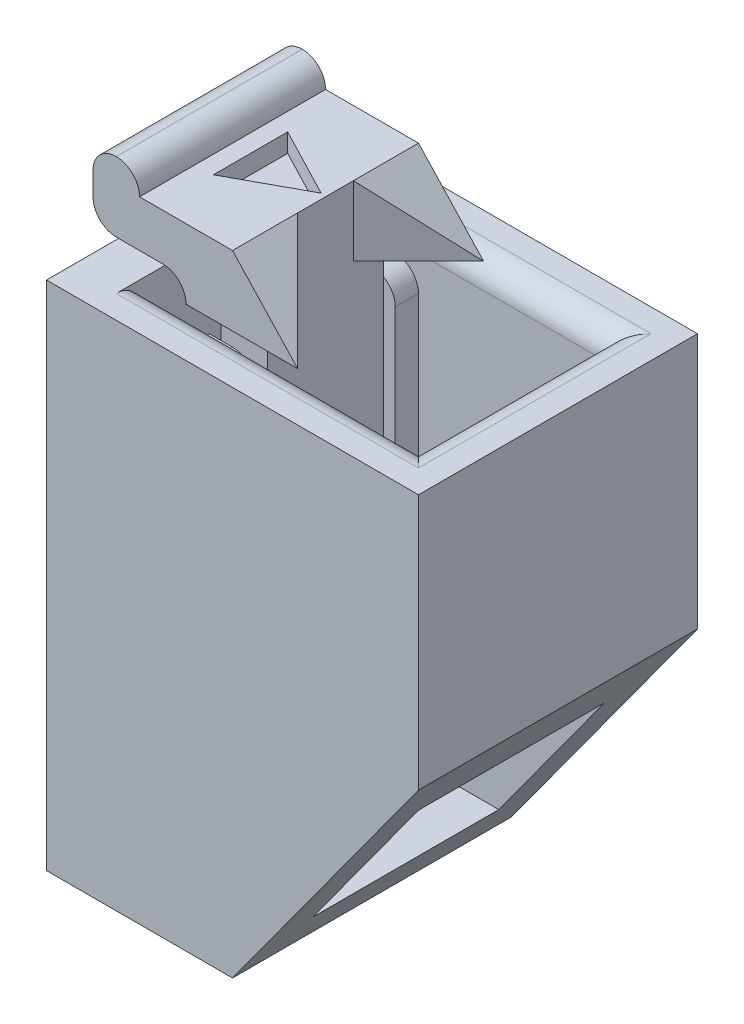
SolidWorks part; units mm, degrees
ref_plane "Front Plane" through (0, 0, 0) normal (0, 0, 1) x (1, 0, 0)
ref_plane "Top Plane" through (0, 0, 0) normal (0, 1, 0) x (1, 0, 0)
ref_plane "Right Plane" through (0, 0, 0) normal (1, 0, 0) x (0, 0, -1)
sketch "BaseSketch" plane through (0, 0, 0) normal (0, 1, 0) x (1, 0, 0)
  line L1 (-6.2677, 3.9685) -> (9.7323, 3.9685)
  line L2 (-6.2677, 3.9685) -> (-6.2677, -8.0315)
  line L3 (-6.2677, -8.0315) -> (9.7323, -8.0315)
  line L4 (9.7323, 3.9685) -> (9.7323, -8.0315)
  dimension "D1" = 16
  dimension "D2" = 12
extrude "BaseExtrude" add sketch "BaseSketch" along normal blind 2
sketch "SlotSketch" plane through (0, 2, 0) normal (0, 1, 0) x (1, 0, 0)
  line L10 (-2.2677, 0.9685) -> (-0.2677, 0.9685)
  line L11 (-2.2677, 1.9685) -> (-4.2677, 1.9685)
  line L12 (-2.2677, 1.9685) -> (-2.2677, 0.9685)
  line L13 (-0.2677, -6.0315) -> (7.7323, -6.0315)
  line L14 (7.7323, -6.0315) -> (7.7323, 1.9685)
  line L15 (-4.2677, -6.0315) -> (7.7323, -6.0315)
  line L16 (-4.2677, 1.9685) -> (-4.2677, -6.0315)
  line L17 (7.7323, 1.9685) -> (-4.2677, 1.9685)
  line L18 (7.7323, -6.0315) -> (7.7323, 1.9685)
  line L19 (-4.2677, -6.0315) -> (-2.2677, -6.0315)
  line L20 (-4.2677, 1.9685) -> (-4.2677, -6.0315)
  line L21 (7.7323, 1.9685) -> (-0.2677, 1.9685)
  line L22 (-0.2677, 1.9685) -> (-0.2677, 0.9685)
  line L23 (-2.2677, -5.0315) -> (-0.2677, -5.0315)
  line L24 (-2.2677, 0.4685) -> (-2.2677, -4.5315)
  line L25 (-2.2677, 0.4685) -> (-0.2677, 0.4685)
  line L26 (-2.2677, 0.4685) -> (-2.2677, -4.5315)
  line L27 (-2.2677, -4.5315) -> (-0.2677, -4.5315)
  line L28 (-0.2677, 0.4685) -> (-0.2677, -4.5315)
  line L29 (-0.2677, 0.4685) -> (-0.2677, -4.5315)
  line L30 (-2.2677, -5.0315) -> (-2.2677, -6.0315)
  line L31 (-0.2677, -5.0315) -> (-0.2677, -6.0315)
  line L33 (-6.2677, 3.9685) -> (9.7323, 3.9685)
  line L34 (-6.2677, 3.9685) -> (-6.2677, -8.0315)
  line L35 (-6.2677, -8.0315) -> (9.7323, -8.0315)
  line L36 (9.7323, 3.9685) -> (9.7323, -8.0315)
  line M5 (-6.2677, 3.9685) -> (-6.2677, -8.0315)
  line M6 (-6.2677, -8.0315) -> (9.7323, -8.0315)
  line M7 (9.7323, -8.0315) -> (9.7323, 3.9685)
  line M8 (9.7323, 3.9685) -> (-6.2677, 3.9685)
  dimension "D2" = 8
  dimension "D3" = 2
  dimension "D4" = 2
  dimension "D5" = 8
  dimension "D6" = 1
  dimension "D7" = 1
  dimension "D8" = 5
  dimension "D9" = 0.5
  dimension "D1" = 2
extrude "FlapExtrude" add sketch "SlotSketch" along normal blind 20.1 contours L25 L28 L27 L24
sketch "HandleBaseSketch" plane through (0, 22.1, 0) normal (0, 1, 0) x (1, 0, 0)
  line L0 (9.7323, 3.9685) -> (-6.2677, 3.9685) construction
  line L1 (-2.2677, 1.9685) -> (-0.2677, 1.9685)
  line L2 (-2.2677, 1.9685) -> (-2.2677, -6.0315)
  line L3 (-2.2677, -6.0315) -> (-0.2677, -6.0315)
  line L4 (-0.2677, 1.9685) -> (-0.2677, -6.0315)
  line L5 (-6.2677, -8.0315) -> (9.7323, -8.0315) construction
  dimension "D1" = 2
  dimension "D2" = 2
extrude "HandleBase" add sketch "HandleBaseSketch" along normal blind 3
sketch "TriangleBaseSketch" plane through (-0.2677, 0, 0) normal (1, 0, 0) x (0, 0, -1)
  line L0 (-6.0315, 22.1) -> (-3.2315, 22.1)
  line L1 (-3.2315, 22.1) -> (-3.2315, 25.1)
  line L2 (-6.0315, 25.1) -> (1.9685, 25.1) construction
  line L3 (-3.2315, 25.1) -> (-6.0315, 25.1)
  line L4 (-6.0315, 25.1) -> (-6.0315, 22.1)
  line L5 (1.9685, 22.1) -> (-0.8315, 22.1)
  line L6 (-0.8315, 22.1) -> (-0.8315, 25.1)
  line L7 (-0.8315, 25.1) -> (1.9685, 25.1)
  line L8 (1.9685, 25.1) -> (1.9685, 22.1)
extrude "PyramidExtrude" add sketch "TriangleBaseSketch" along normal blind 2.8
sketch "PyramidSideCutSketch" plane through (0, 0, -1.9685) normal (0, 0, -1) x (-1, 0, 0)
  line L0 (-2.5323, 22.1) -> (0.2677, 25.1)
  line L1 (0.2677, 25.1) -> (-2.5323, 25.1)
  line L2 (-2.5323, 25.1) -> (-2.5323, 22.1)
sketch "PyramidTopCutSketch" plane through (0, 25.1, 0) normal (0, 1, 0) x (1, 0, 0)
  line L0 (-0.2677, -3.2315) -> (2.5323, -6.0315)
  line L1 (2.5323, -6.0315) -> (2.5323, -3.2315)
  line L2 (2.5323, -3.2315) -> (-0.2677, -3.2315)
  line L3 (-0.2677, -0.8315) -> (2.5323, 1.9685)
  line L4 (2.5323, 1.9685) -> (2.5323, -0.8315)
  line L5 (2.5323, -0.8315) -> (-0.2677, -0.8315)
extrude "PyramidTopCut" cut sketch "PyramidTopCutSketch" against normal blind 3
extrude "PyramidSideCut" cut sketch "PyramidSideCutSketch" against normal through all contours L0 L1 L2
extrude "Boss-Extrude5" add sketch "SlotSketch<6>" along normal blind 3 contours L31 L23 L30 L19 L20 L11 L12 L10 L22 L21 L18 L13 M8 M5 M6 M7 | L12 L10 L22 L21 L18 L13 L31 L23 L30 L19 L20 L11 | L33 L36 L35 L34 region at (-1.2677, 2, -1.4685) region at (-1.2677, 2, 5.5315) region at (1.7323, 2, -3.7685)
sketch "SlotSketch<6>" plane through (0, 2, 0) normal (0, 1, 0) x (1, 0, 0) same geometry as "SlotSketch"
extrude "Sides" add sketch "SlotSketch<7>" along normal blind 20 contours L11 L20 L19 L30 L23 L31 L13 L18 L21 L22 L10 L12 | L33 L36 L35 L34
sketch "SlotSketch<7>" plane through (0, 2, 0) normal (0, 1, 0) x (1, 0, 0) same geometry as "SlotSketch"
sketch "Sketch7" plane through (-0.2677, 0, 0) normal (1, 0, 0) x (0, 0, -1)
  line L0 (-5.0315, 22) -> (-5.0315, 2) construction
  line L1 (-6.0315, 22) -> (-5.0315, 22)
  line L2 (-6.0315, 22) -> (-6.0315, 20.4974)
  line L3 (-6.0315, 20.4974) -> (-5.0315, 20.4974)
  line L4 (-5.0315, 22) -> (-5.0315, 20.4974)
  line L5 (1.9685, 22) -> (1.9685, 2) construction
  line L6 (0.9685, 22) -> (1.9685, 22)
  line L7 (0.9685, 22) -> (0.9685, 20.4974)
  line L8 (0.9685, 20.4974) -> (1.9685, 20.4974)
  line L9 (1.9685, 22) -> (1.9685, 20.4974)
extrude "WallClearanceCut" cut sketch "Sketch7" against normal blind 2
sketch "BaseTriangleCutSketch" plane through (0, 0, 8.0315) normal (0, 0, 1) x (1, 0, 0)
  line L0 (9.7323, 0) -> (1.7323, 0)
  line L1 (-6.2677, 0) -> (9.7323, 0) construction
  line L2 (1.7323, 0) -> (9.7323, 11)
  line L3 (9.7323, 22) -> (9.7323, 0) construction
  line L4 (9.7323, 11) -> (9.7323, 0)
extrude "BaseTriangleCut" cut sketch "BaseTriangleCutSketch" against normal through all
sketch "Sketch9" plane through (-2.2677, 0, 0) normal (-1, 0, 0) x (0, 0, 1)
  line L0 (6.0315, 25.1) -> (6.0315, 22.1) construction
  line L1 (-1.9685, 25.1) -> (6.0315, 25.1)
  line L2 (-1.9685, 25.1) -> (-1.9685, 23.1)
  line L3 (-1.9685, 23.1) -> (6.0315, 23.1)
  line L4 (6.0315, 25.1) -> (6.0315, 23.1)
extrude "Handle" add sketch "Sketch9" along normal blind 4
sketch "Sketch10" plane through (0, 25.1, 0) normal (0, 1, 0) x (1, 0, 0)
  line L0 (-0.2677, 1.9685) -> (-6.2677, 1.9685) construction
  line L1 (-6.2677, -6.0315) -> (-4.2659, -6.0315)
  line L2 (-6.2677, -6.0315) -> (-6.2677, 1.9685)
  line L3 (-6.2677, 1.9685) -> (-4.2659, 1.9685)
  line L4 (-4.2659, -6.0315) -> (-4.2659, 1.9685)
extrude "Boss-Extrude8" add sketch "Sketch10" along normal blind 1
sketch "WashHoleSketch" plane through (-6.2677, 0, 0) normal (-1, 0, 0) x (0, 0, 1)
  line L0 (-3.9685, 22) -> (-3.9685, 0) construction
  line L1 (-1.9685, 18) -> (6.0315, 18)
  line L2 (-1.9685, 18) -> (-1.9685, 4)
  line L3 (-1.9685, 4) -> (6.0315, 4)
  line L4 (6.0315, 18) -> (6.0315, 4)
  line L5 (8.0315, 22) -> (8.0315, 0) construction
  line L6 (-3.9685, 22) -> (8.0315, 22) construction
  line L7 (-3.9685, 0) -> (8.0315, 0) construction
  dimension "D1" = 2
  dimension "D2" = 2
  dimension "D3" = 4
  dimension "D4" = 4
extrude "WashHole" cut sketch "WashHoleSketch" against normal blind 2
fillet "Fillet1" radius 1 10 edges at (1.7323, 22, -1.9685) (1.7323, 22, 6.0315) (7.7323, 22, 2.0315) (-2.2677, 2, 2.0315) (-2.2677, 23.1, 2.0315) (-6.2677, 23.1, 2.0315) (-4.2659, 26.1, 2.0315) (-6.2677, 26.1, 2.0315) (-0.2677, 20.4974, -1.4685) (-0.2677, 20.4974, 5.5315)
sketch "MarkerSketch" plane through (0, 25.1, 0) normal (0, 1, 0) x (1, 0, 0)
  line L0 (-0.4994, -1.9893) -> (-3.4984, -0.4264)
  line L1 (-3.4984, -0.4264) -> (-3.4984, -3.6225)
  line L2 (-3.4984, -3.6225) -> (-0.4994, -1.9893)
extrude "Cut-Extrude6" cut sketch "MarkerSketch" against normal blind 0.8
